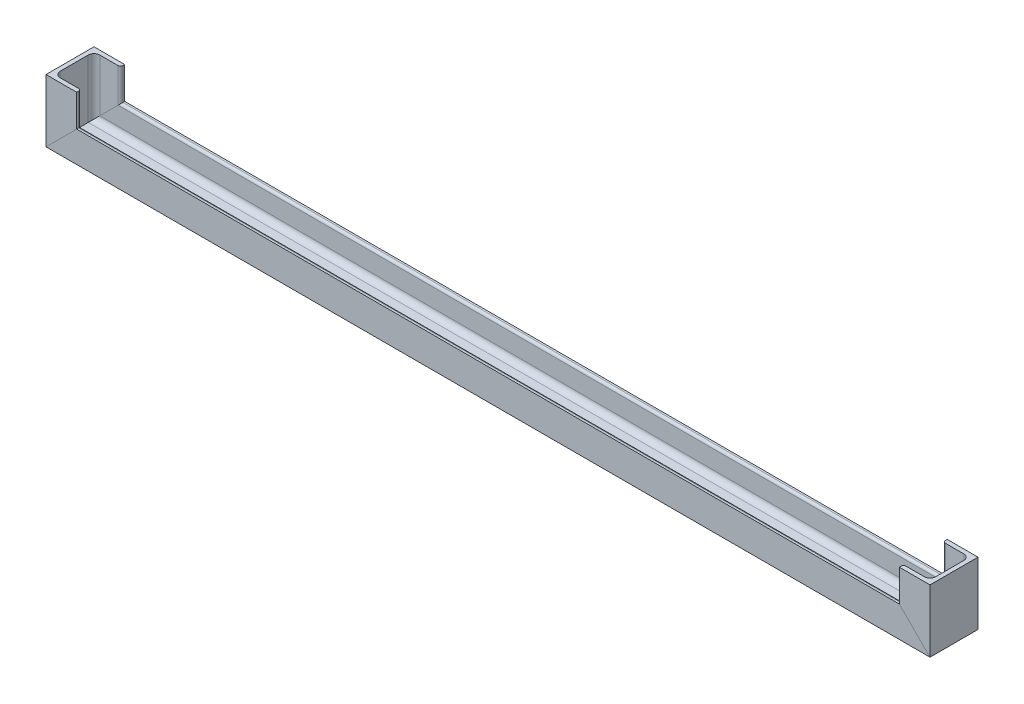
SolidWorks part; units mm, degrees
note: The reader was unsure of these and kept them because the rebuilt part matched: shared geometry of "Эскиз2<3>".
material "AISI 1020"
ref_plane "Спереди" through (0, 0, 0) normal (0, 0, 1) x (1, 0, 0)
ref_plane "Сверху" through (0, 0, 0) normal (0, 1, 0) x (1, 0, 0)
ref_plane "Справа" through (0, 0, 0) normal (1, 0, 0) x (0, 0, -1)
sketch "Эскиз1" plane through (0, 0, 0) normal (0, 0, 1) x (1, 0, 0)
  line L0 (-460.4, 69.25) -> (-460.4, 4)
  line L1 (-460.4, 69.25) -> (-460.4, -0.75) construction
  line L2 (-460.4, 4) -> (0, 4)
  line L3 (-422.0653, 0) -> (-325.0653, 0) construction
  line L4 (0, -1000) -> (0, 49000) construction
  dimension "D1" = 4
sketch "Эскиз2" plane through (0, 69.25, 0) normal (0, -1, 0) x (1, 0, 0)
  line L0 (-460.4, 132.5) -> (-460.4, -567.5) construction
  line B0 (-460.4, -25) -> (-460.4, 25)
  line B1 (-460.4, 25) -> (-428.4, 25)
  line B2 (-428.4, 25) -> (-428.4, 23.1)
  line B3 (-430.9, 20.6) -> (-450, 20.6)
  line B4 (-456, 14.6) -> (-456, -14.6)
  line B5 (-430.9, -20.6) -> (-450, -20.6)
  line B6 (-428.4, -25) -> (-428.4, -23.1)
  line B7 (-460.4, -25) -> (-428.4, -25)
  arc B8 (-450, 20.6) -> (-456, 14.6) centre (-450, 14.6) ccw
  arc B9 (-428.4, 23.1) -> (-430.9, 20.6) centre (-430.9, 23.1) cw
  arc B10 (-428.4, -23.1) -> (-430.9, -20.6) centre (-430.9, -23.1) ccw
  arc B11 (-450, -20.6) -> (-456, -14.6) centre (-450, -14.6) cw
sketch_block_instance "Швеллер 5У (ГОСТ 8240-97)-1"
sketch_block "Швеллер 5У (ГОСТ 8240-97)" parameters "D3"=6, "D4"=2.5, "D1"=4.4, "D2"=32
ref_plane "Плоскость1" through (0, 4, 0) normal (0, 1, 0) x (1, 0, 0)
sketch "Эскиз3" plane through (0, 4, 0) normal (0, 1, 0) x (1, 0, 0)
  line L0 (-460.4, 0) -> (-285.0653, 0)
  line L1 (-460.4, 0) -> (0, 0) construction
  line L2 (-285.0653, 0) -> (-263.4147, -12.5)
  line L3 (-263.4147, -12.5) -> (0, -12.5)
  line L4 (8, -38.5) -> (-8, -38.5) construction
  line L5 (-305.0653, -32.5) -> (-305.0653, 32.5) construction
  dimension "D1" = 25
  dimension "D2" = 26
  dimension "D3" = 20
  dimension "D4" = 30
sketch3d "Трехмерный эскиз1"
  line L0 (-460.4, 69.25, 0) -> (-460.4, 4, 0)
  line L1 (-263.4147, 4, 12.5) -> (0, 4, 12.5) construction
  line L2 (-285.0653, 4, 0) -> (-263.4147, 4, 12.5) construction
  line L3 (-460.4, 4, 0) -> (-285.0653, 4, 0) construction
  line L4 (-263.4147, 4, 12.5) -> (0, 4, 12.5)
  line L5 (-285.0653, 4, 0) -> (-263.4147, 4, 12.5)
  line L6 (-460.4, 4, 0) -> (-285.0653, 4, 0)
sketch3d "Трехмерный эскиз2"
  line L0 (-460.4, 69.25, 0) -> (-460.4, 4, 0) construction
  line L1 (-460.4, 4, 0) -> (0, 4, 0) construction
  line L2 (-460.4, 69.25, 0) -> (-460.4, 4, 0)
  line L3 (-460.4, 4, 0) -> (0, 4, 0)
sweep "По траектории2" [suppressed] add profiles "Эскиз2" path "Трехмерный эскиз1"
other "Полость1" [suppressed]
other "Кулак привода<1>@ТП.SH21-600(К1).000 - Концепт 1 ARM600"
mirror "Зеркальное отражение1" [suppressed]
sweep "По траектории4" add profiles "Эскиз2<3>" path "Трехмерный эскиз2"
sketch "Эскиз2<3>" plane through (0, 69.25, 0) normal (0, -1, 0) x (1, 0, 0) same geometry as "Эскиз2"
mirror "Зеркальное отражение2" about plane through (0, 33.5, 23.1) normal (-1, 0, 0) of bodies 107
equation "\"D2@Эскиз3\"=\"D1@Эскиз3\"+1"
